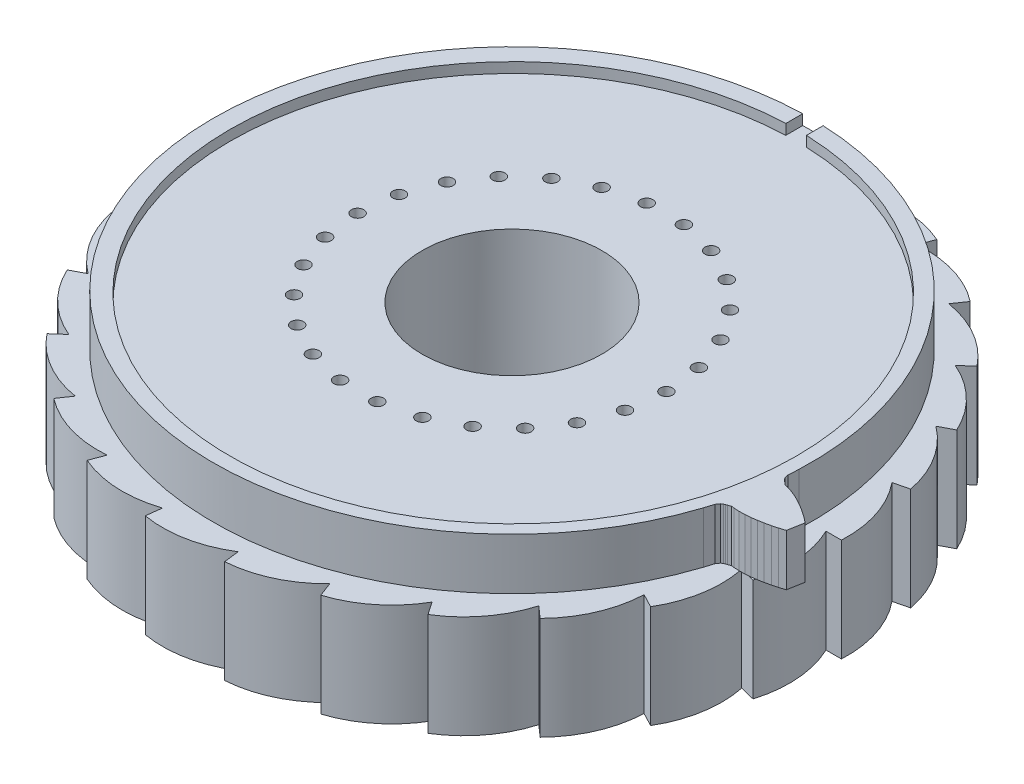
SolidWorks part; units mm, degrees
material "1060 Alloy"
ref_plane "Front Plane" through (0, 0, 0) normal (0, 0, 1) x (1, 0, 0)
ref_plane "Top Plane" through (0, 0, 0) normal (0, 1, 0) x (1, 0, 0)
ref_plane "Right Plane" through (0, 0, 0) normal (1, 0, 0) x (0, 0, -1)
sketch "Sketch1" plane through (0, 0, 0) normal (0, 1, 0) x (1, 0, 0)
  line L0 (0, 0) -> (54.8903, 0) construction
  line L1 (0, 0) -> (47.5263, 11.7142) construction
  line L2 (0, 0) -> (29.6137, 7.2991)
  line L3 (0, 0) -> (32, 0)
  circle A0 centre (0, 0) radius 32 construction
  circle A1 centre (0, 0) radius 30.5 construction
  arc A2 (29.6137, 7.2991) -> (32, 0) centre (21.3514, 0.5583) cw
  circle A3 centre (0, 0) radius 31.25 construction
  dimension "D1" = 62.5
  dimension "D2" = 1.5
  dimension "D4" = 0.75
  dimension "D3" = 13.846
extrude "Extrude ratchet edge" add sketch "Sketch1" along normal blind 10
pattern_circular "Pattern edge to form gear" count 26 over 360 about axis through (0, 10, 0) along (0, -1, 0) of "Extrude ratchet edge" reverse direction yes
sketch "Sketch12" plane through (0, 10, 0) normal (0, 1, 0) x (1, 0, 0)
  line L0 (28.9274, -2.1257) -> (29.0264, -2.5152)
  line L1 (29.0264, -2.5152) -> (29.1427, -2.6718)
  line L2 (29.1427, -2.6718) -> (29.2623, -2.7873)
  line L3 (29.2623, -2.7873) -> (29.3837, -2.8801)
  line L4 (29.3837, -2.8801) -> (29.6242, -3.0821)
  line L5 (29.6242, -3.0821) -> (29.8792, -3.1399)
  line L6 (29.8792, -3.1399) -> (30.3843, -3.2992)
  line L7 (30.3843, -3.2992) -> (30.8844, -3.4996)
  line L8 (30.8844, -3.4996) -> (31.3799, -3.7334)
  line L9 (31.3799, -3.7334) -> (31.8708, -3.9966)
  line L10 (31.8708, -3.9966) -> (32.3568, -4.2867)
  line L11 (32.3568, -4.2867) -> (32.8378, -4.602)
  line L12 (32.8378, -4.602) -> (33.3134, -4.9413)
  line L13 (33.3134, -4.9413) -> (33.7833, -5.3035)
  line L14 (33.7833, -5.3035) -> (33.502, -6.8593)
  line L15 (33.502, -6.8593) -> (32.9351, -7.0341)
  line L16 (32.9351, -7.0341) -> (32.3708, -7.1854)
  line L17 (32.3708, -7.1854) -> (31.8099, -7.3124)
  line L18 (31.8099, -7.3124) -> (31.253, -7.414)
  line L19 (31.253, -7.414) -> (30.7011, -7.4887)
  line L20 (30.7011, -7.4887) -> (30.1551, -7.5342)
  line L21 (30.1551, -7.5342) -> (29.6165, -7.5468)
  line L22 (29.6165, -7.5468) -> (29.0876, -7.5192)
  line L23 (29.0876, -7.5192) -> (28.8285, -7.4842)
  line L24 (28.8285, -7.4842) -> (28.5325, -7.5891)
  line L25 (28.5325, -7.5891) -> (28.3863, -7.6336)
  line L26 (28.3863, -7.6336) -> (28.2339, -7.6999)
  line L27 (28.2339, -7.6999) -> (28.07, -7.8059)
  line L28 (28.07, -7.8059) -> (27.841, -8.136)
  line L29 (27.841, -8.136) -> (27.578, -8.987)
  line L779 (28.9844, -1.1053) -> (28.9274, -2.1257)
  arc A0 (27.578, -8.987) -> (28.9844, -1.1053) centre (0, 0) cw
extrude "Gear face" add sketch "Sketch12" along normal blind 5
sketch "Sketch7" plane through (0, 15, 0) normal (0, 1, 0) x (1, 0, 0)
  circle A0 centre (0, 0) radius 8.7313
  dimension "D1" = 17.4625
sketch "Sketch10" plane through (0, 15, 0) normal (0, 1, 0) x (1, 0, 0)
  line L0 (-0.7538, 29.3517) -> (-0.7538, 27.3517)
  line L1 (1.2462, 27.3517) -> (1.2462, 29.3517)
  line L2 (1.2462, 29.3517) -> (-0.7538, 29.3517)
  line L3 (0.2462, -0.1301) -> (0.2462, 41.1735) construction
  line L4 (0.2462, -0.1301) -> (0.2462, 36.6199) construction
  arc A0 (-0.7538, 27.3517) -> (1.2462, 27.3517) centre (0.2462, -0.1301) ccw
  dimension "D1" = 2
extrude "PCB inset" cut sketch "Sketch10" against normal blind 1
extrude "Cut bearing hole" cut sketch "Sketch7" against normal through all
sketch "Sketch11" plane through (0, 0, 0) normal (0, -1, 0) x (1, 0, 0)
  line L0 (1, -29.4818) -> (1, -27.4818)
  line L1 (-1, -27.4818) -> (-1, -29.4818)
  line L2 (-1, -29.4818) -> (1, -29.4818)
  line L3 (0, 0) -> (0, -100.666) construction
  arc A0 (1, -27.4818) -> (-1, -27.4818) centre (0, 0) ccw
  point P0 (0, -29.4818)
  dimension "D2" = 2
  dimension "D3" = 27.5
  dimension "D1" = 2
  dimension "D4" = 2
extrude "PCB inset rear" cut sketch "Sketch11" against normal blind 1
sketch "pin holes" plane through (0, 14, 0) normal (0, 1, 0) x (1, 0, 0)
  circle A0 centre (15, 0) radius 0.6
  circle A1 centre (14.5641, -3.5897) radius 0.6
  circle A2 centre (13.2818, -6.9708) radius 0.6
  circle A3 centre (11.2277, -9.9468) radius 0.6
  circle A4 centre (8.521, -12.3448) radius 0.6
  circle A5 centre (5.3191, -14.0252) radius 0.6
  circle A6 centre (1.8081, -14.8906) radius 0.6
  circle A7 centre (-1.8081, -14.8906) radius 0.6
  circle A8 centre (-5.3191, -14.0252) radius 0.6
  circle A9 centre (-8.521, -12.3448) radius 0.6
  circle A10 centre (-11.2277, -9.9468) radius 0.6
  circle A11 centre (-13.2818, -6.9708) radius 0.6
  circle A12 centre (-14.5641, -3.5897) radius 0.6
  circle A13 centre (-15, 0) radius 0.6
  circle A14 centre (-14.5641, 3.5897) radius 0.6
  circle A15 centre (-13.2818, 6.9708) radius 0.6
  circle A16 centre (-11.2277, 9.9468) radius 0.6
  circle A17 centre (-8.521, 12.3448) radius 0.6
  circle A18 centre (-5.3191, 14.0252) radius 0.6
  circle A19 centre (-1.8081, 14.8906) radius 0.6
  circle A20 centre (1.8081, 14.8906) radius 0.6
  circle A21 centre (5.3191, 14.0252) radius 0.6
  circle A22 centre (8.521, 12.3448) radius 0.6
  circle A23 centre (11.2277, 9.9468) radius 0.6
  circle A24 centre (13.2818, 6.9708) radius 0.6
  circle A25 centre (14.5641, 3.5897) radius 0.6
  point P55 (0, 0)
  dimension "D1" = 1.2
  dimension "D2" = 15
  dimension "D3" = 26
extrude "Pin holes cut" cut sketch "pin holes" against normal through all
equation "\"Bearing size\"= 17.4625mm"
equation "\"D1@Sketch7\" = \"Bearing size\""
equation "\"dedendum\"= 2mm"
equation "\"addendum\"= 2mm"
equation "\"D5@Iteration wheel\" = \"addendum\""
equation "\"base diameter\"=58"
equation "\"alpha\"= sqr ( ( \"base diameter\" + \"dedendum\" ) ^ 2 - \"base diameter\" ^ 2 ) / \"base diameter\" * 180 / PI - \"phi\""
equation "\"phi\"= 20"
